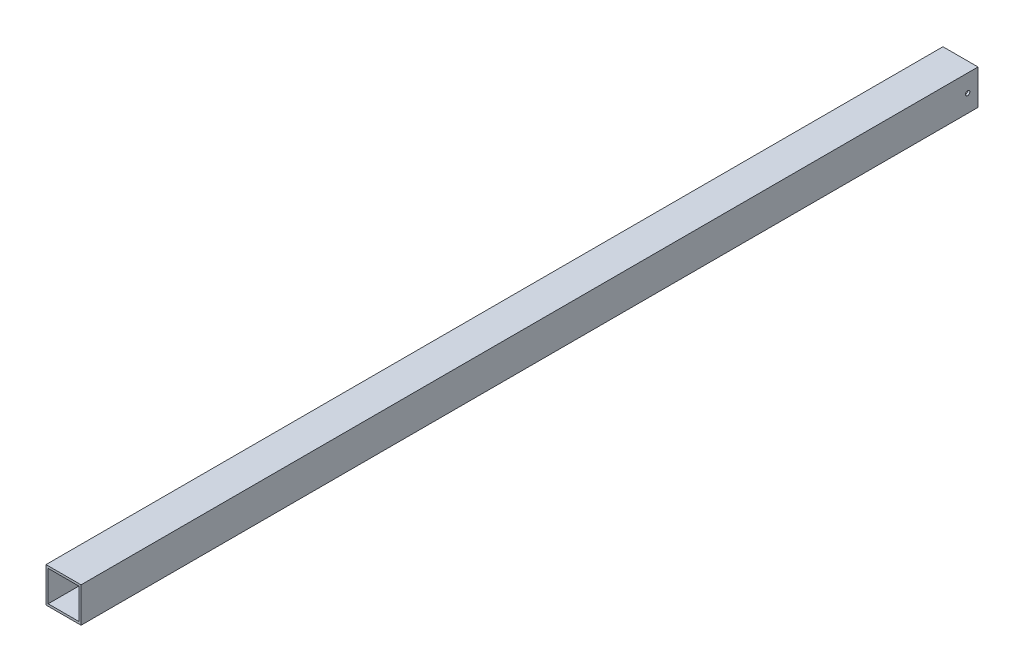
SolidWorks part; units mm, degrees
ref_plane "Plan de face" through (0, 0, 0) normal (0, 0, 1) x (1, 0, 0)
ref_plane "Plan de dessus" through (0, 0, 0) normal (0, 1, 0) x (1, 0, 0)
ref_plane "Plan de droite" through (0, 0, 0) normal (1, 0, 0) x (0, 0, -1)
sketch "Esquisse2" plane through (0, 0, 0) normal (0, 0, 1) x (1, 0, 0)
  line L1 (-25.4, 25.4) -> (25.4, 25.4)
  line L2 (-25.4, 25.4) -> (-25.4, -25.4)
  line L3 (-25.4, -25.4) -> (25.4, -25.4)
  line L4 (25.4, 25.4) -> (25.4, -25.4)
  line L5 (-25.4, 25.4) -> (25.4, -25.4) construction
  line L6 (-25.4, -25.4) -> (25.4, 25.4) construction
  line L7 (-22.225, 22.225) -> (22.225, 22.225)
  line L8 (-22.225, 22.225) -> (-22.225, -22.225)
  line L9 (-22.225, -22.225) -> (22.225, -22.225)
  line L10 (22.225, 22.225) -> (22.225, -22.225)
  line L11 (-22.225, 22.225) -> (22.225, -22.225) construction
  line L12 (-22.225, -22.225) -> (22.225, 22.225) construction
  point P0 (0, 0)
  point P6 (0, 0)
  dimension "D1" = 50.8
  dimension "D2" = 3.175
  dimension "D3" = 3.175
extrude "Boss.-Extru.1" add sketch "Esquisse2" along normal mid plane 1300
sketch "Esquisse4" plane through (-25.4, 0, 0) normal (-1, 0, 0) x (0, 0, 1)
  line L0 (650, 25.4) -> (-650, 25.4) construction
  line L3 (-650, 25.4) -> (-650, -25.4) construction
  circle A0 centre (-635, 0) radius 3.175
  dimension "D1" = 6.35
  dimension "D2" = 25.4
  dimension "D3" = 15
extrude "Enlèv. mat.-Extru.2" cut sketch "Esquisse4" against normal through all
hole_wizard "M4 Clearance Hole1" positions "Sketch1" profile "Sketch2" hole size "M4" standard "ANSI Metric" end condition up to next
sketch "Sketch1" plane through (-25.4, 0, 0) normal (-1, 0, 0) x (0, 0, 1)
  point P0 (517.1, -3.175)
  point P3 (557.1, -3.175)
  point P6 (597.1, -3.175)
sketch "Sketch2" plane through (-25.4, -3.175, 517.1) normal (0, 1, 0) x (0, 0, 1)
  line L0 (0, 0) -> (0, 3.175)
  line L1 (0, 3.175) -> (2.25, 3.175)
  line L2 (2.25, 3.175) -> (2.25, 0.175)
  line L3 (2.25, 0.175) -> (2.425, 0)
  line L5 (2.425, 0) -> (0, 0)
  line L6 (-2.25, 0.175) -> (-2.425, 0) construction
  line L11 (0, -6.35) -> (0, 107.95) construction
  dimension "Thru Hole Dia." = 4.5
  dimension "Thru Hole Depth" = 3.175
  dimension "Near C'Sink Dia." = 4.85
  dimension "Near C'Sink Angle" = 90
equation "\"D1@Boss.-Extru.1\"=1300mm"
